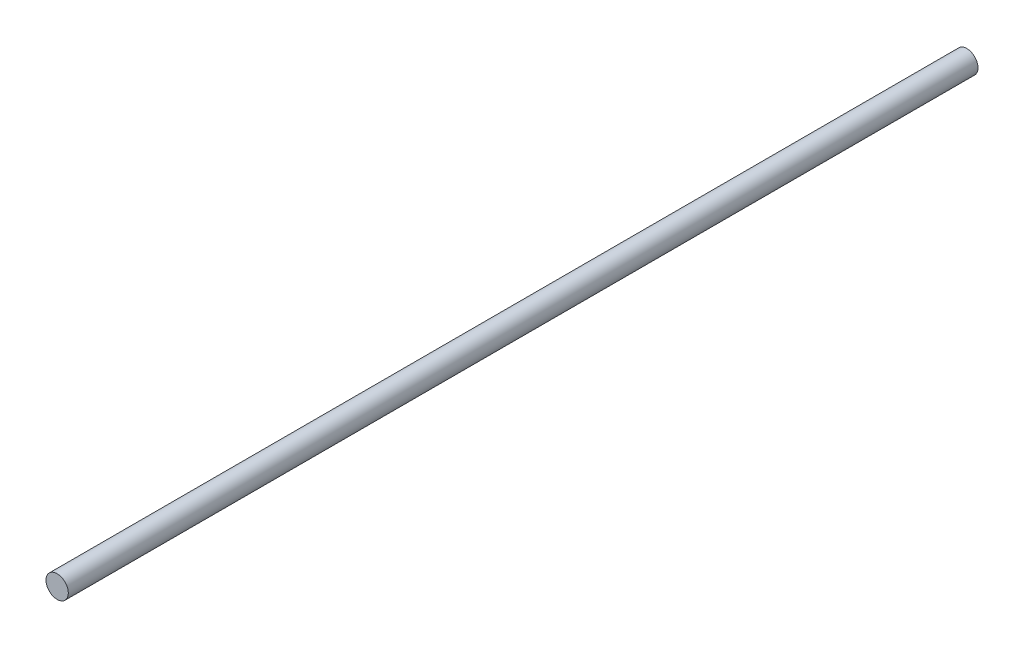
SolidWorks part; units mm, degrees
material "AISI 316 Stainless Steel Sheet (SS)"
ref_plane "Front (1)" through (0, 0, 0) normal (0, 0, 1) x (1, 0, 0)
ref_plane "Top (2)" through (0, 0, 0) normal (0, 1, 0) x (1, 0, 0)
ref_plane "Right (3)" through (0, 0, 0) normal (1, 0, 0) x (0, 0, -1)
ref_axis "X Axis" through (13.5064, 0, 0) along (-1, 0, 0)
ref_axis "Y Axis" through (0, 12.3593, 0) along (0, -1, 0)
ref_axis "Z Axis" through (0, 0, 14.1119) along (0, 0, -1)
sketch "Sketch2" plane through (0, 0, 0) normal (1, 0, 0) x (0, 0, -1)
  line L0 (-7.8, 0) -> (0, 0) construction
  line L1 (-7.8, 0) -> (318.0477, 0)
  line L2 (-7.8, 0) -> (-7.8, 4)
  line L3 (-7.8, 4) -> (318.0477, 4)
  line L4 (318.0477, 0) -> (318.0477, 4)
  dimension "D1" = 8
  dimension "D2" = 325.8477
revolve "Revolve1" add sketch "Sketch2" angle 360 about L0
